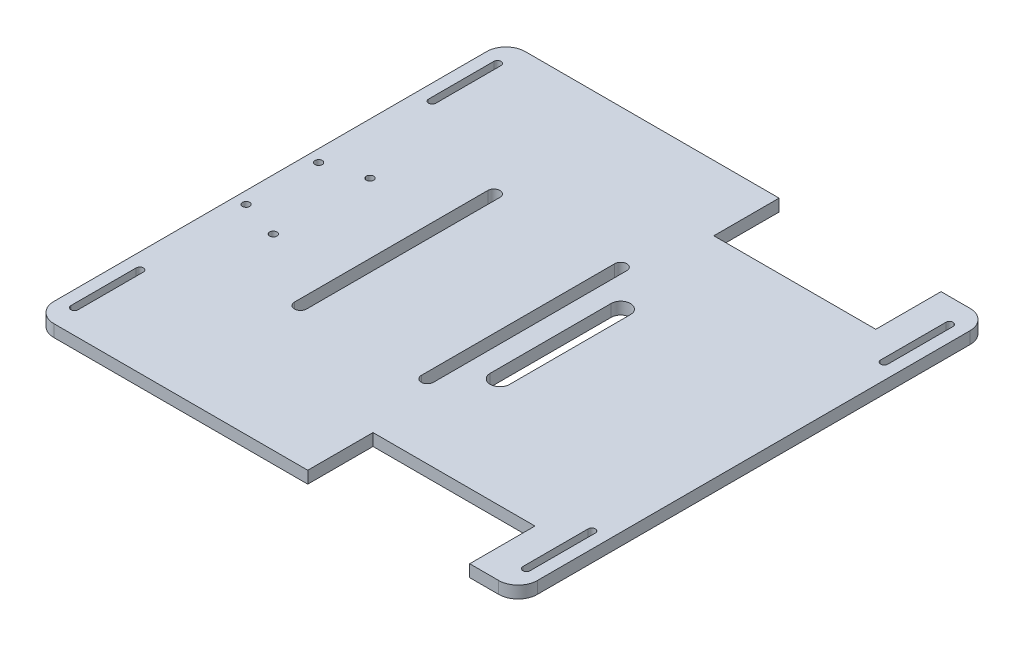
SolidWorks part; units mm, degrees
ref_plane "Front Plane" through (0, 0, 0) normal (0, 0, 1) x (1, 0, 0)
ref_plane "Top Plane" through (0, 0, 0) normal (0, 1, 0) x (1, 0, 0)
ref_plane "Right Plane" through (0, 0, 0) normal (1, 0, 0) x (0, 0, -1)
sketch "Sketch2" plane through (0, 0, 0) normal (0, 1, 0) x (1, 0, 0)
  line L1 (-100, -97.5) -> (100, -97.5)
  line L2 (-100, -97.5) -> (-100, 97.5)
  line L3 (-100, 97.5) -> (100, 97.5)
  line L4 (100, -97.5) -> (100, 97.5)
  line L5 (-100, -97.5) -> (100, 97.5) construction
  line L6 (-100, 97.5) -> (100, -97.5) construction
  point P0 (0, 0)
  dimension "D1" = 200
  dimension "D2" = 195
extrude "Boss-Extrude1" add sketch "Sketch2" along normal blind 5
sketch "Sketch3" plane through (0, 5, 0) normal (0, 1, 0) x (1, 0, 0)
  line L0 (-100, 0) -> (100, 0) construction
  line L1 (-100, 97.5) -> (-100, -97.5) construction
  line L2 (100, -97.5) -> (100, 97.5) construction
  line L3 (0, -97.5) -> (0, 97.5) construction
  line L4 (-100, -97.5) -> (100, -97.5) construction
  line L5 (100, 97.5) -> (-100, 97.5) construction
  line L6 (-93.5, -87.5) -> (-93.5, -60.5) construction
  line L7 (-95, -87.5) -> (-95, -60.5)
  line L8 (-92, -87.5) -> (-92, -60.5)
  line L9 (-93.5, 87.5) -> (-93.5, 60.5) construction
  line L10 (-95, 87.5) -> (-95, 60.5)
  line L11 (-92, 87.5) -> (-92, 60.5)
  line L12 (93.5, 87.5) -> (93.5, 60.5) construction
  line L13 (95, 87.5) -> (95, 60.5)
  line L14 (92, 87.5) -> (92, 60.5)
  line L15 (93.5, -87.5) -> (93.5, -60.5) construction
  line L16 (95, -87.5) -> (95, -60.5)
  line L17 (92, -87.5) -> (92, -60.5)
  arc A0 (-95, -87.5) -> (-92, -87.5) centre (-93.5, -87.5) ccw
  arc A1 (-92, -60.5) -> (-95, -60.5) centre (-93.5, -60.5) ccw
  arc A2 (-95, 87.5) -> (-92, 87.5) centre (-93.5, 87.5) cw
  arc A3 (-92, 60.5) -> (-95, 60.5) centre (-93.5, 60.5) cw
  arc A4 (95, 87.5) -> (92, 87.5) centre (93.5, 87.5) ccw
  arc A5 (92, 60.5) -> (95, 60.5) centre (93.5, 60.5) ccw
  arc A6 (95, -87.5) -> (92, -87.5) centre (93.5, -87.5) cw
  arc A7 (92, -60.5) -> (95, -60.5) centre (93.5, -60.5) cw
  point P14 (-93.5, -74)
  point P21 (-93.5, 74)
  point P28 (93.5, 74)
  point P35 (93.5, -74)
  dimension "D2" = 1.5
  dimension "D3" = 5
  dimension "D4" = 10
  dimension "D1" = 27
extrude "Cut-Extrude1" cut sketch "Sketch3" against normal through all
sketch "Sketch4" plane through (0, 0, 0) normal (0, -1, 0) x (1, 0, 0)
  line L0 (-100, 0) -> (100, 0) construction
  line L1 (-100, -97.5) -> (-100, 97.5) construction
  line L2 (100, 97.5) -> (100, -97.5) construction
  line L3 (100, -97.5) -> (-100, -97.5) construction
  line L4 (13, -97.5) -> (80, -97.5)
  line L5 (13, -97.5) -> (13, -70.5)
  line L6 (13, -70.5) -> (80, -70.5)
  line L7 (80, -97.5) -> (80, -70.5)
  line L8 (80, 97.5) -> (80, 70.5)
  line L9 (13, 97.5) -> (80, 97.5)
  line L10 (13, 70.5) -> (80, 70.5)
  line L11 (13, 97.5) -> (13, 70.5)
  line L12 (-47.5, 40) -> (-47.5, -40) construction
  line L13 (-45, 40) -> (-45, -40)
  line L14 (-50, 40) -> (-50, -40)
  line L15 (20, 25) -> (20, -25) construction
  line L16 (24, 25) -> (24, -25)
  line L17 (16, 25) -> (16, -25)
  line L18 (100, 97.5) -> (100, -97.5) construction
  line L19 (-100, -97.5) -> (-100, 97.5) construction
  line L20 (5, 40) -> (5, -40) construction
  line L21 (7.5, 40) -> (7.5, -40)
  line L22 (2.5, 40) -> (2.5, -40)
  arc A0 (-45, 40) -> (-50, 40) centre (-47.5, 40) ccw
  arc A1 (-50, -40) -> (-45, -40) centre (-47.5, -40) ccw
  arc A2 (24, 25) -> (16, 25) centre (20, 25) ccw
  arc A3 (16, -25) -> (24, -25) centre (20, -25) ccw
  arc A4 (7.5, 40) -> (2.5, 40) centre (5, 40) ccw
  arc A5 (2.5, -40) -> (7.5, -40) centre (5, -40) ccw
  point P18 (-47.5, 0)
  point P25 (20, 0)
  point P36 (5, 0)
  dimension "D5" = 2.5
  dimension "D8" = 4
  dimension "D11" = 2.5
  dimension "D1" = 27
  dimension "D2" = 67
  dimension "D3" = 20
  dimension "D4" = 80
  dimension "D6" = 55
  dimension "D7" = 50
  dimension "D9" = 80
  dimension "D10" = 80
  dimension "D12" = 50
extrude "Cut-Extrude2" cut sketch "Sketch4" against normal through all
sketch "Sketch8" plane through (0, 5, 0) normal (0, 1, 0) x (1, 0, 0)
  line L0 (-100, 0) -> (100, 0) construction
  line L1 (-100, 97.5) -> (-100, -97.5) construction
  line L2 (100, -97.5) -> (100, 97.5) construction
  line L3 (-78.75, -25) -> (-78.75, 25) construction
  line L4 (-95, -25) -> (-62.5, -25)
  line L5 (-95, -25) -> (-95, 25)
  line L6 (-95, 25) -> (-62.5, 25)
  line L7 (-62.5, -25) -> (-62.5, 25)
  line L8 (-95, -25) -> (-62.5, 25) construction
  line L9 (-95, 25) -> (-62.5, -25) construction
  circle A0 centre (-78.75, -19.995) radius 1.5
  circle A1 centre (-78.75, 19.995) radius 1.5
  point P6 (-78.75, 0)
  dimension "D4" = 3
  dimension "D1" = 32.5
  dimension "D2" = 50
  dimension "D3" = 5
  dimension "D5" = 39.99
extrude "Cut-Extrude6" cut sketch "Sketch8" against normal through all contours A1 | A0 region at (-78.75, 5, -19.995)
sketch "Sketch9" plane through (0, 5, 0) normal (0, 1, 0) x (1, 0, 0)
  line L0 (-100, 0) -> (100, 0) construction
  line L1 (-100, 97.5) -> (-100, -97.5) construction
  line L2 (100, -97.5) -> (100, 97.5) construction
  line L4 (-100, -25) -> (-90, -25)
  line L5 (-100, -25) -> (-100, 25)
  line L6 (-100, 25) -> (-90, 25)
  line L7 (-90, -25) -> (-90, 25)
  line L8 (-100, -25) -> (-90, 25) construction
  line L9 (-100, 25) -> (-90, -25) construction
  circle A0 centre (-95, 15) radius 1.5
  circle A1 centre (-95, -15) radius 1.5
  point P6 (-95, 0)
  dimension "D4" = 3
  dimension "D1" = 10
  dimension "D2" = 0
  dimension "D3" = 50
  dimension "D5" = 30
  dimension "D6" = 5
extrude "Cut-Extrude7" cut sketch "Sketch9" against normal through all contours A0 | A1
fillet "Fillet1" radius 8 4 edges at (100, 2.5, -97.5) (100, 2.5, 97.5) (-100, 2.5, -97.5) (-100, 2.5, 97.5)
